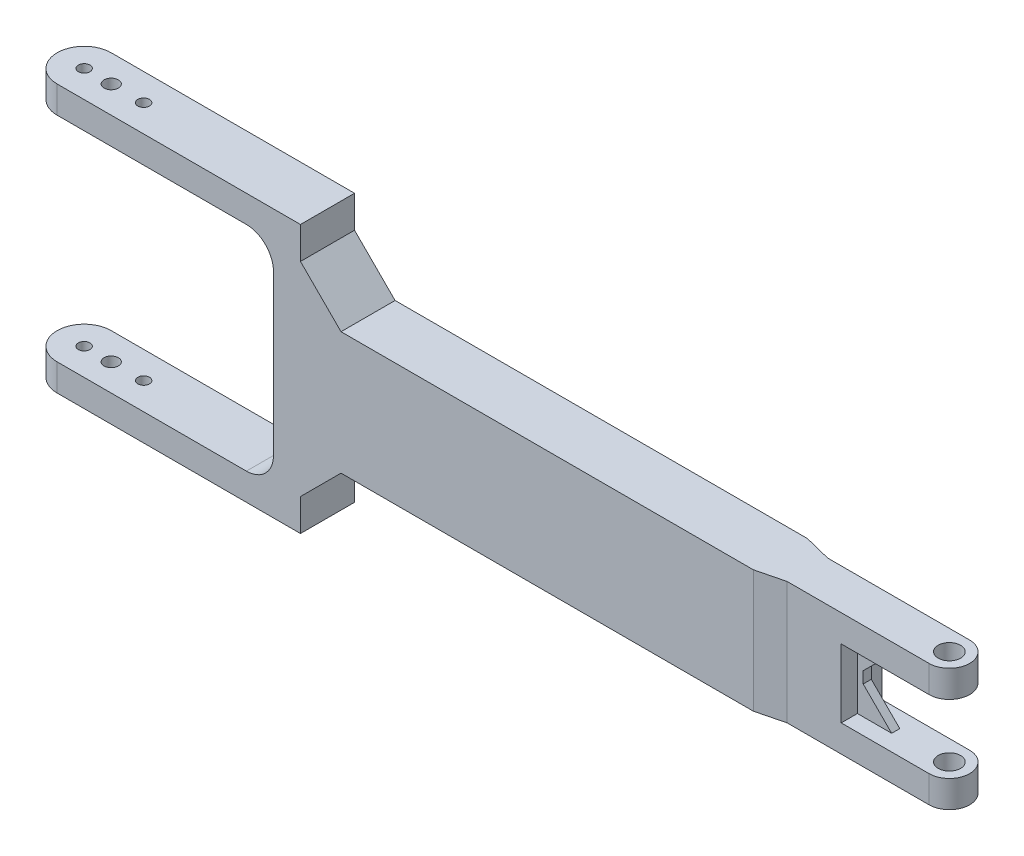
SolidWorks part; units mm, degrees
material "ABS"
ref_plane "前视基准面" through (0, 0, 0) normal (0, 0, 1) x (1, 0, 0)
ref_plane "上视基准面" through (0, 0, 0) normal (0, 1, 0) x (1, 0, 0)
ref_plane "右视基准面" through (0, 0, 0) normal (1, 0, 0) x (0, 0, -1)
other "Configuration Table"
sketch "草图2" plane through (0, 0, 0) normal (0, 0, 1) x (1, 0, 0)
  line L0 (0, 12.65) -> (0, -12.65)
  line L1 (0, 12.65) -> (40, 12.65)
  line L2 (40, 12.65) -> (40, 22.65)
  line L3 (40, 22.65) -> (-10, 22.65)
  line L4 (-10, 22.65) -> (-10, -22.65)
  line L5 (-10, -22.65) -> (40, -22.65)
  line L6 (40, -22.65) -> (40, -12.65)
  line L7 (40, -12.65) -> (0, -12.65)
  line L8 (-207.5, -39.5) -> (-207.5, 39.5)
  line L9 (-207.5, -39.5) -> (-297.5, -39.5)
  line L10 (-297.5, -39.5) -> (-297.5, -49.5)
  line L11 (-297.5, -49.5) -> (-197.5, -49.5)
  line L12 (-197.5, -49.5) -> (-197.5, 49.5)
  line L13 (-197.5, 49.5) -> (-297.5, 49.5)
  line L14 (-297.5, 49.5) -> (-297.5, 39.5)
  line L15 (-297.5, 39.5) -> (-207.5, 39.5)
  line L16 (-10, 22.65) -> (-197.5, 22.65)
  line L17 (-10, -22.65) -> (-197.5, -22.65)
  line L18 (0, 0) -> (12.65, 12.65)
  line L19 (0, 0) -> (12.65, -12.65)
  point P4 (0, 0)
  point P12 (-207.5, 0)
  dimension "D1" = 25.3
  dimension "D2" = 40
  dimension "D3" = 10
  dimension "D4" = 10
  dimension "D5" = 79
  dimension "D6" = 90
  dimension "D7" = 10
  dimension "D8" = 10
  dimension "D9" = 10
  dimension "D10" = 187.5
  dimension "D11" = 45
extrude "凸台-拉伸1" add sketch "草图2" along normal mid plane 20 contours L17 L4 L16 L12 | L14 L15 L8 L9 L10 L11 L12 L13 region at (-103.75, 0, 0) region at (-198.9072, 0, 0)
extrude "凸台-拉伸2" add sketch "草图2<3>" along normal mid plane 15 contours L6 L7 L0 L1 L2 L3 L4 L5 region at (-0.6747, 6.325, 0)
sketch "草图2<3>" plane through (0, 0, 0) normal (0, 0, 1) x (1, 0, 0) same geometry as "草图2"
chamfer "倒角1" distance 20 distance2 5 1 edges at (-10, 0, 10) first distance on face at (-201.25, 0, 10)
chamfer "倒角2" distance 5 distance2 20 1 edges at (-10, 0, -10) first distance on face at (-10, 0, -8.75)
extrude "凸台-拉伸3" add sketch "草图2<5>" along normal mid plane 3 contours L0 L18 L1 | L19 L0 L7 region at (4.2167, 8.4333, 0) region at (4.2167, -8.4333, 0)
sketch "草图2<5>" plane through (0, 0, 0) normal (0, 0, 1) x (1, 0, 0) same geometry as "草图2"
chamfer "倒角3" distance 3 angle 45 1 edges at (0, 0, 0)
sketch "草图3" plane through (0, 49.5, 0) normal (0, 1, 0) x (1, 0, 0)
  line L0 (-297.5, 0) -> (-197.5, 0) construction
  line L4 (-197.5, 10) -> (-297.5, 10)
  line L5 (-297.5, 10) -> (-297.5, -10)
  line L6 (-297.5, -10) -> (-197.5, -10)
  line L7 (-197.5, -10) -> (-197.5, 10)
  line L8 (-197.5, 10) -> (-297.5, 10)
  line L9 (-297.5, 10) -> (-297.5, -10)
  line L10 (-297.5, -10) -> (-197.5, -10)
  line L11 (-197.5, -10) -> (-197.5, 10)
  circle A0 centre (-277.5, 0) radius 2.65
  circle A1 centre (-287.5, 0) radius 2.15
  circle A2 centre (-265.5, 0) radius 2.15
  arc A3 (-287.5, 10) -> (-287.5, -10) centre (-287.5, 0) ccw
  line M6 (-297.5, 10) -> (-297.5, -10)
  line M7 (-297.5, -10) -> (-197.5, -10)
  dimension "D2" = 5.3
  dimension "D5" = 4.3
  dimension "D7" = 180
  dimension "D3" = 10
  dimension "D4" = 12
  dimension "D6" = 80
  dimension "D1" = 0
extrude "切除-拉伸1" cut sketch "草图3" against normal through all contours A3 L8 M6 | A3 L9 M7 | L0 A1 | A1 L0 | A0 L0 | L0 A0 | A2 L0 | L0 A2 region at (-265.5, 49.5, 0.9125) region at (-265.5, 49.5, -0.9125) region at (-277.5, 49.5, 1.1247) region at (-277.5, 49.5, -1.1247) region at (-295.2663, 49.5, 7.7663) region at (-295.2663, 49.5, -7.7663) region at (-287.5, 49.5, 0.9125) region at (-287.5, 49.5, -0.9125)
sketch "草图4" plane through (0, 22.65, 0) normal (0, 1, 0) x (1, 0, 0)
  line L0 (0, 0) -> (40, 0) construction
  line L1 (40, -7.5) -> (40, 7.5) construction
  line L8 (40, 7.5) -> (-20, 7.5)
  line L9 (-20, 7.5) -> (-30, 10)
  line L10 (-30, 10) -> (-197.5, 10)
  line L11 (-197.5, 10) -> (-197.5, -10)
  line L12 (-197.5, -10) -> (-30, -10)
  line L13 (-30, -10) -> (-20, -7.5)
  line L14 (-20, -7.5) -> (40, -7.5)
  line L15 (40, -7.5) -> (40, 7.5)
  line L16 (40, 7.5) -> (-20, 7.5)
  line L17 (-20, 7.5) -> (-30, 10)
  line L18 (-30, 10) -> (-197.5, 10)
  line L19 (-197.5, 10) -> (-197.5, -10)
  line L20 (-197.5, -10) -> (-30, -10)
  line L21 (-30, -10) -> (-20, -7.5)
  line L22 (-20, -7.5) -> (40, -7.5)
  line L23 (40, -7.5) -> (40, 7.5)
  circle A0 centre (32.5, 0) radius 7.5
  circle A1 centre (32.5, 0) radius 4.15
  line M10 (40, 7.5) -> (-20, 7.5)
  line M17 (40, -7.5) -> (40, 7.5)
  dimension "D2" = 8.3
  dimension "D1" = 0
extrude "切除-拉伸2" cut sketch "草图4" against normal through all contours A1 L0 | L0 A1 | A0 L23 M10 | A0 L22 M17 region at (32.5, 22.65, 1.7613) region at (32.5, 22.65, -1.7613) region at (38.3247, 22.65, -5.8247) region at (38.3247, 22.65, 5.8247)
chamfer "倒角4" distance 15 angle 45 2 edges at (-197.5, -22.65, 0) (-197.5, 22.65, 0)
fillet "圆角1" radius 10 2 edges at (-207.5, 39.5, 0) (-207.5, -39.5, 0)
